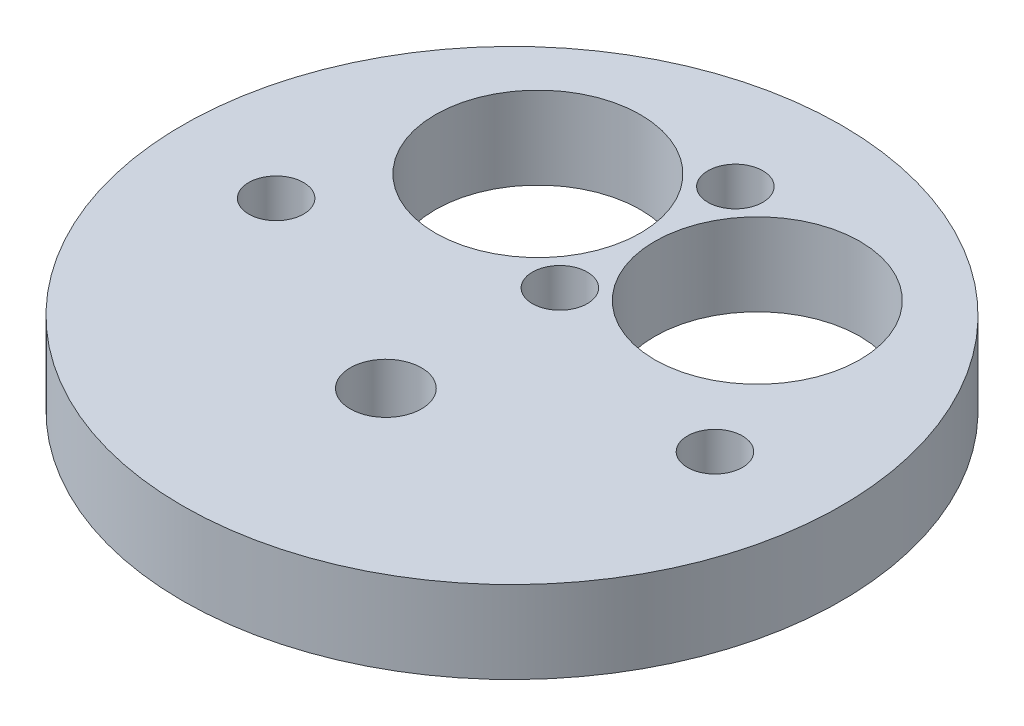
SolidWorks part; units mm, degrees
ref_plane "Front Plane" through (0, 0, 0) normal (0, 0, 1) x (1, 0, 0)
ref_plane "Top Plane" through (0, 0, 0) normal (0, 1, 0) x (1, 0, 0)
ref_plane "Right Plane" through (0, 0, 0) normal (1, 0, 0) x (0, 0, -1)
ref_axis "Axis1" through (0, 55, 0) along (0, -1, 0)
sketch "Sketch1" plane through (0, 0, 0) normal (0, 0, 1) x (1, 0, 0)
  line L0 (0, 0) -> (38.1508, 0)
  line L3 (38.1508, 0) -> (38.1508, 9.525)
  line L4 (38.1508, 9.525) -> (0, 9.525)
  line L5 (0, 55) -> (0, -55) construction
  line L6 (0, 9.525) -> (0, 0)
  line L7 (0, 0) -> (0, 21.2966) construction
  point P3 (38.1508, 0)
  point P10 (38.1508, 0.1463)
  dimension "D1" = 76.3016
  dimension "D2" = 9.525
revolve "Revolve1" add sketch "Sketch1" angle 360 about L7
sketch "Sketch2" plane through (0, 9.525, 0) normal (0, 1, 0) x (1, 0, 0)
  line L0 (-12.7, 15.6993) -> (12.7, 15.6993) construction
  line L1 (0, 25.8593) -> (0, 5.5393) construction
  line L2 (-12.7, 15.6993) -> (12.7, 15.6993) construction
  line L3 (-12.7, 29.6693) -> (12.7, 29.6693) construction
  line L4 (-12.7, 1.7293) -> (12.7, 1.7293) construction
  circle A0 centre (-12.7, 15.6993) radius 11.8745
  circle A1 centre (0, 0) radius 38.1508
  circle A3 centre (12.7, 15.6993) radius 11.8745
  circle A4 centre (0, 25.8593) radius 3.175
  circle A5 centre (0, 5.5393) radius 3.175
  arc A6 (-12.7, 29.6693) -> (-12.7, 1.7293) centre (-12.7, 15.6993) ccw construction
  arc A7 (12.7, 1.7293) -> (12.7, 29.6693) centre (12.7, 15.6993) ccw construction
  circle A8 centre (0, -14.605) radius 4.1275
  circle A9 centre (0, 0) radius 34.163 construction
  circle A11 centre (0, 0) radius 38.1508 construction
  point P11 (0, 15.6993)
  point P12 (0, 15.6993)
  point P15 (0, 15.6993)
  dimension "D2" = 23.749
  dimension "D3" = 23.749
  dimension "D5" = 6.35
  dimension "D6" = 6.35
  dimension "D11" = 8.255
  dimension "D4" = 25.4
  dimension "D7" = 20.32
  dimension "D8" = 25.4
  dimension "D9" = 27.94
  dimension "D10" = 14.605
  dimension "D1" = 0
extrude "Cut-Extrude1" cut sketch "Sketch2" against normal through all both and the other way through all
sketch "Sketch3" plane through (0, 9.525, 0) normal (0, 1, 0) x (1, 0, 0)
  circle A0 centre (-25.4, -1.905) radius 3.175
  circle A1 centre (25.4, -1.905) radius 3.175
  circle A2 centre (0, -14.605) radius 4.1275 construction
  dimension "D1" = 6.35
  dimension "D2" = 6.35
  dimension "D3" = 50.8
  dimension "D4" = 12.7
  dimension "D5" = 1.905
extrude "Cut-Extrude2" cut sketch "Sketch3" against normal through all both
ref_plane "Plane1" through (0, 4.7625, 0) normal (0, 1, 0) x (-1, 0, 0)
equation "\"D3@Sketch2\"=\"D2@Sketch2\""
equation "\"D6@Sketch2\"=\"D5@Sketch2\""
